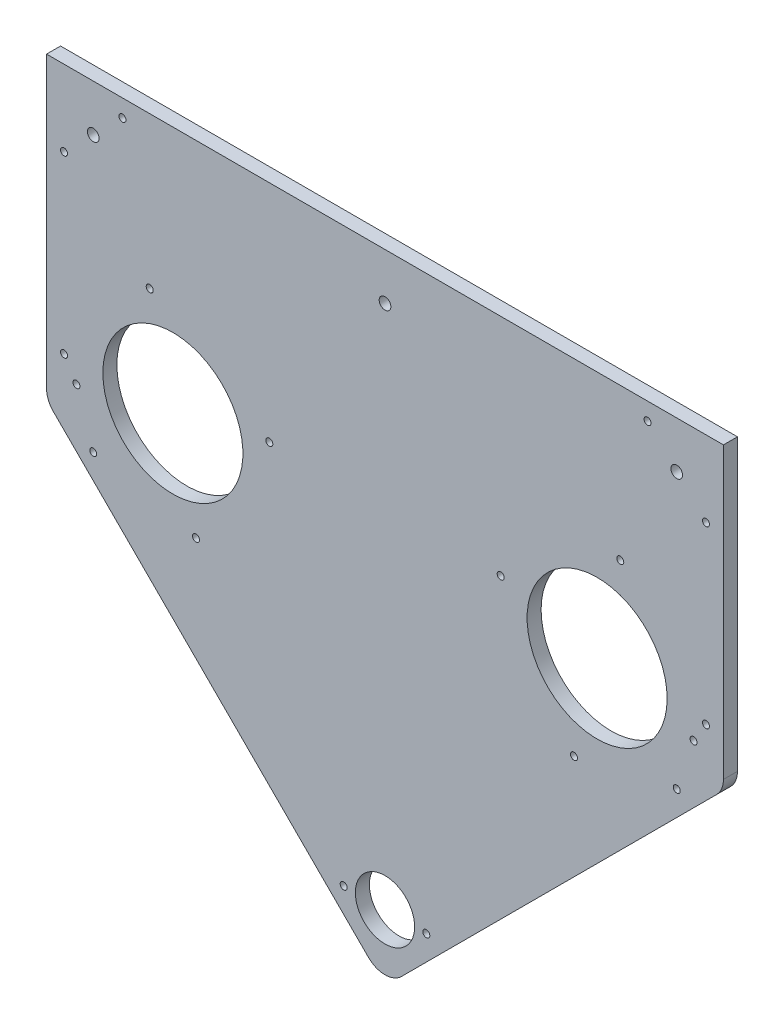
SolidWorks part; units mm, degrees
ref_plane "Front Plane" through (0, 0, 0) normal (0, 0, 1) x (1, 0, 0)
ref_plane "Top Plane" through (0, 0, 0) normal (0, 1, 0) x (1, 0, 0)
ref_plane "Right Plane" through (0, 0, 0) normal (1, 0, 0) x (0, 0, -1)
sketch "Sketch1" plane through (0, 0, 0) normal (0, 0, 1) x (1, 0, 0)
  line L0 (-125, 100) -> (125, 100) construction
  line L1 (-125, 0) -> (125, 0) construction
  line L2 (-137.5158, 87.4842) -> (-125, 100) construction
  line L3 (0, -125) -> (-125, 0) construction
  line L4 (0, -125) -> (-17.7, -125) construction
  line L5 (-125, -17.7) -> (-125, 0) construction
  line L6 (0, -125) -> (0, 100) construction
  line L7 (-145, 120) -> (145, 120)
  line L8 (145, 120) -> (145, -8.2843)
  line L9 (145, -8.2843) -> (0, -153.2843)
  line L10 (0, -153.2843) -> (-145, -8.2843)
  line L11 (-145, -8.2843) -> (-145, 120)
  circle A0 centre (-125, 100) radius 12.7 construction
  circle A1 centre (125, 100) radius 12.7 construction
  circle A4 centre (0, -125) radius 12.7
  circle A5 centre (-137.5158, 87.4842) radius 1.5
  circle A6 centre (-112.4842, 112.5158) radius 1.5
  circle A7 centre (-137.5158, 12.5158) radius 1.5
  circle A8 centre (-125, -17.7) radius 1.5
  circle A9 centre (-17.7, -125) radius 1.5
  circle A10 centre (-125, 0) radius 12.7 construction
  circle A11 centre (125, 0) radius 12.7 construction
  circle A12 centre (-125, 0) radius 17.7 construction
  circle A13 centre (-125, 100) radius 17.7 construction
  circle A14 centre (0, -125) radius 17.7 construction
  circle A15 centre (17.7, -125) radius 1.5
  circle A16 centre (125, -17.7) radius 1.5
  circle A17 centre (137.5158, 12.5158) radius 1.5
  circle A18 centre (137.5158, 87.4842) radius 1.5
  circle A19 centre (112.4842, 112.5158) radius 1.5
  circle A20 centre (0, 100) radius 2.5
  circle A21 centre (-125, 100) radius 2.5
  circle A22 centre (125, 100) radius 2.5
  point P12 (0, 100)
  point P45 (0, 120)
  dimension "D1" = 25.4
  dimension "D5" = 3
  dimension "D2" = 5
  dimension "D4" = 100
  dimension "D6" = 5
  dimension "D7" = 135
  dimension "D8" = 45
  dimension "D9" = 250
  dimension "D10" = 45
  dimension "D11" = 20
  dimension "D12" = 20
  dimension "D13" = 20
  dimension "D14" = 20
  dimension "D15" = 20
  dimension "D3" = 125
extrude "Boss-Extrude1" add sketch "Sketch1" along normal blind 6
fillet "Fillet1" radius 10 3 edges at (-145, -8.2843, 3) (145, -8.2843, 3) (0, -153.2843, 3)
sketch "Sketch2" plane through (0, 0, 6) normal (0, 0, 1) x (1, 0, 0)
  line L0 (132.2073, 3.8685) -> (49.5554, 23.7093) construction
  line L1 (80.961, -27.5371) -> (100.8017, 55.1149) construction
  line L2 (0, 0) -> (0, 100) construction
  circle A0 centre (90.8813, 13.7889) radius 42.5 construction
  circle A1 centre (49.5554, 23.7093) radius 1.5
  circle A2 centre (100.8017, 55.1149) radius 1.5
  circle A3 centre (132.2073, 3.8685) radius 1.5
  circle A4 centre (80.961, -27.5371) radius 1.5
  circle A5 centre (90.8813, 13.7889) radius 30
  circle A6 centre (-49.5554, 23.7093) radius 1.5
  circle A7 centre (-100.8017, 55.1149) radius 1.5
  circle A8 centre (-80.961, -27.5371) radius 1.5
  circle A9 centre (-132.2073, 3.8685) radius 1.5
  circle A10 centre (-90.8813, 13.7889) radius 42.5 construction
  circle A11 centre (-90.8813, 13.7889) radius 30
  point P6 (90.8813, 13.7889)
  point P27 (-90.8813, 13.7889)
  dimension "D1" = 85
  dimension "D2" = 3
  dimension "D3" = 60
extrude "Cut-Extrude1" cut sketch "Sketch2" against normal blind 10
equation "\"carbon_fiber_tube_diam\"= 1in"
equation "\"clip_tube_diam\"= 6mm"
equation "\"D1@Sketch1\"=\"carbon_fiber_tube_diam\""
equation "\"middle_tube_len\"= 500mm"
equation "\"horizontal_pipe_spacing\"= 250mm"
equation "\"D9@Sketch1\"=\"horizontal_pipe_spacing\""
